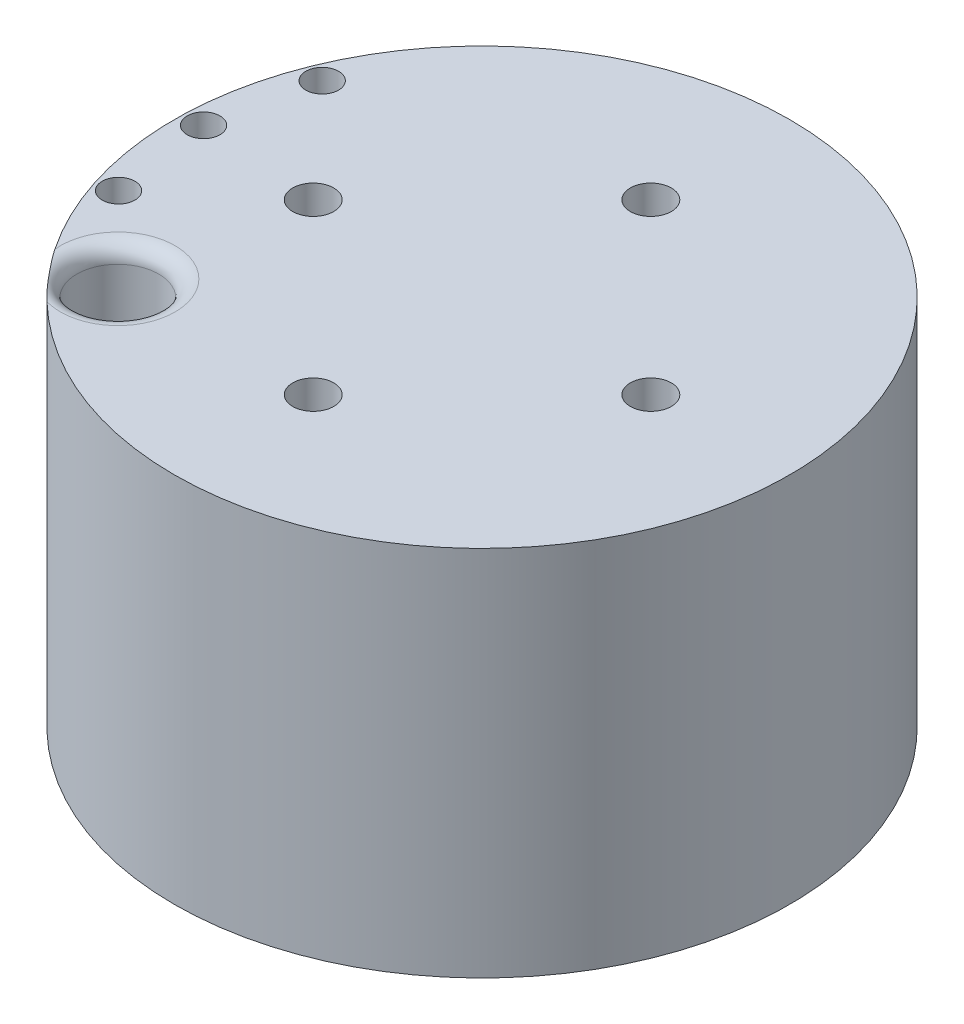
SolidWorks part; units mm, degrees
ref_plane "Front Plane" through (0, 0, 0) normal (0, 0, 1) x (1, 0, 0)
ref_plane "Top Plane" through (0, 0, 0) normal (0, 1, 0) x (1, 0, 0)
ref_plane "Right Plane" through (0, 0, 0) normal (1, 0, 0) x (0, 0, -1)
sketch "Sketch2" plane through (0, 0, 0) normal (0, 1, 0) x (1, 0, 0)
  circle A0 centre (0, 0) radius 47.6885
  dimension "D1" = 95.377
extrude "Boss-Extrude1" add sketch "Sketch2" along normal blind 57.658
sketch "Sketch4" plane through (0, 57.658, 0) normal (0, 1, 0) x (1, 0, 0)
  circle A1 centre (-26.162, 0) radius 3.175
  circle A2 centre (26.162, 0) radius 3.175
  circle A3 centre (0, 26.162) radius 3.175
  circle A4 centre (0, -26.162) radius 3.175
sketch "Sketch5" plane through (0, 57.658, 0) normal (0, 1, 0) x (1, 0, 0)
  line L0 (0, 0) -> (-44.6487, 1.4926)
  line L1 (0, 0) -> (-41.4455, 16.6734)
  line L2 (0, 0) -> (-42.4665, -13.8681)
  line L4 (0, 0) -> (-30.6943, -25.7555)
  circle A1 centre (-41.4455, 16.6734) radius 2.54
  circle A2 centre (0, 0) radius 44.6736
  circle A3 centre (-44.6487, 1.4926) radius 2.54
  circle A4 centre (-42.4665, -13.8681) radius 2.54
  circle A9 centre (-30.6943, -25.7555) radius 6.35
  dimension "D3" = 12.7
  dimension "D5" = 89.3472
  dimension "D1" = 20
  dimension "D2" = 20
  dimension "D6" = 21.915
  dimension "D4" = 40.0685
extrude "Cut-Extrude2" cut sketch "Sketch5" against normal through all contours A9 | A1 | A3 | A4
fillet "Fillet1" radius 2.54 1 edges at (-30.6943, 57.658, 32.1055)
extrude "Cut-Extrude3" cut sketch "Sketch4" against normal through all
equation "\"D4@Sketch5\"=(3.755/2)-(0.5/2)-0.05"
